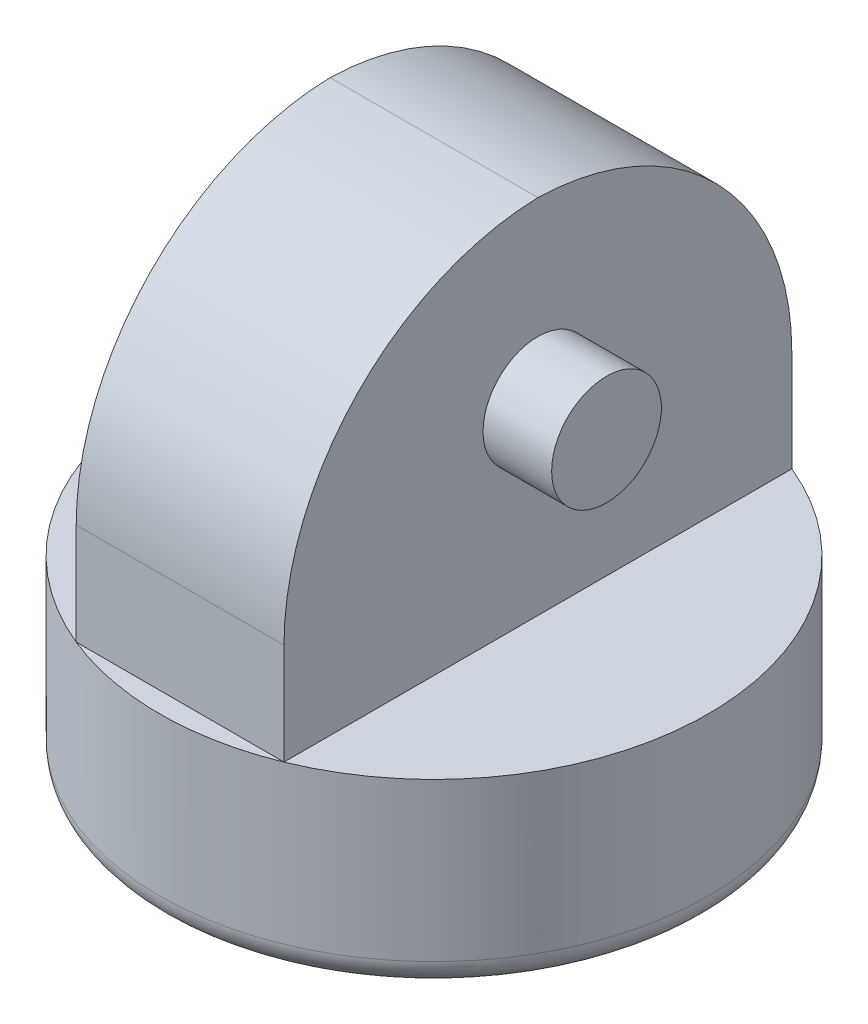
SolidWorks part; units mm, degrees
ref_plane "Alzado" through (0, 0, 0) normal (0, 0, 1) x (1, 0, 0)
ref_plane "Planta" through (0, 0, 0) normal (0, 1, 0) x (1, 0, 0)
ref_plane "Vista lateral" through (0, 0, 0) normal (1, 0, 0) x (0, 0, -1)
sketch "Croquis1" plane through (0, 0, 0) normal (0, 1, 0) x (1, 0, 0)
  circle A0 centre (0, 0) radius 20
extrude "Saliente-Extruir1" add sketch "Croquis1" along normal blind 13.5
fillet "Redondeo1" radius 2 1 edges at (0, 0, 20)
sketch "Croquis2" plane through (0, 13.5, 0) normal (0, 1, 0) x (1, 0, 0)
  line L1 (-7.5747, 18.5101) -> (7.5747, 18.5101)
  line L2 (-7.5747, 18.5101) -> (-7.5747, -18.5101)
  line L3 (-7.5747, -18.5101) -> (7.5747, -18.5101)
  line L4 (7.5747, 18.5101) -> (7.5747, -18.5101)
  line L5 (-7.5747, 18.5101) -> (7.5747, -18.5101) construction
  line L6 (-7.5747, -18.5101) -> (7.5747, 18.5101) construction
  circle A0 centre (0, 0) radius 20 construction
  point P0 (0, 0)
extrude "Saliente-Extruir2" add sketch "Croquis2" along normal blind 26.39
sketch "Croquis3" plane through (-7.5747, 0, 0) normal (-1, 0, 0) x (0, 0, 1)
  line L0 (18.5101, 13.5) -> (-18.5101, 13.5) construction
  circle A0 centre (0, 27.11) radius 4
  dimension "D2" = 8
  dimension "D1" = 13.61
extrude "Saliente-Extruir3" add sketch "Croquis3" along normal blind 5 and the other way blind 20.15
fillet "Redondeo2" radius 19 2 edges at (0, 39.89, 18.5101) (0, 39.89, -18.5101)
